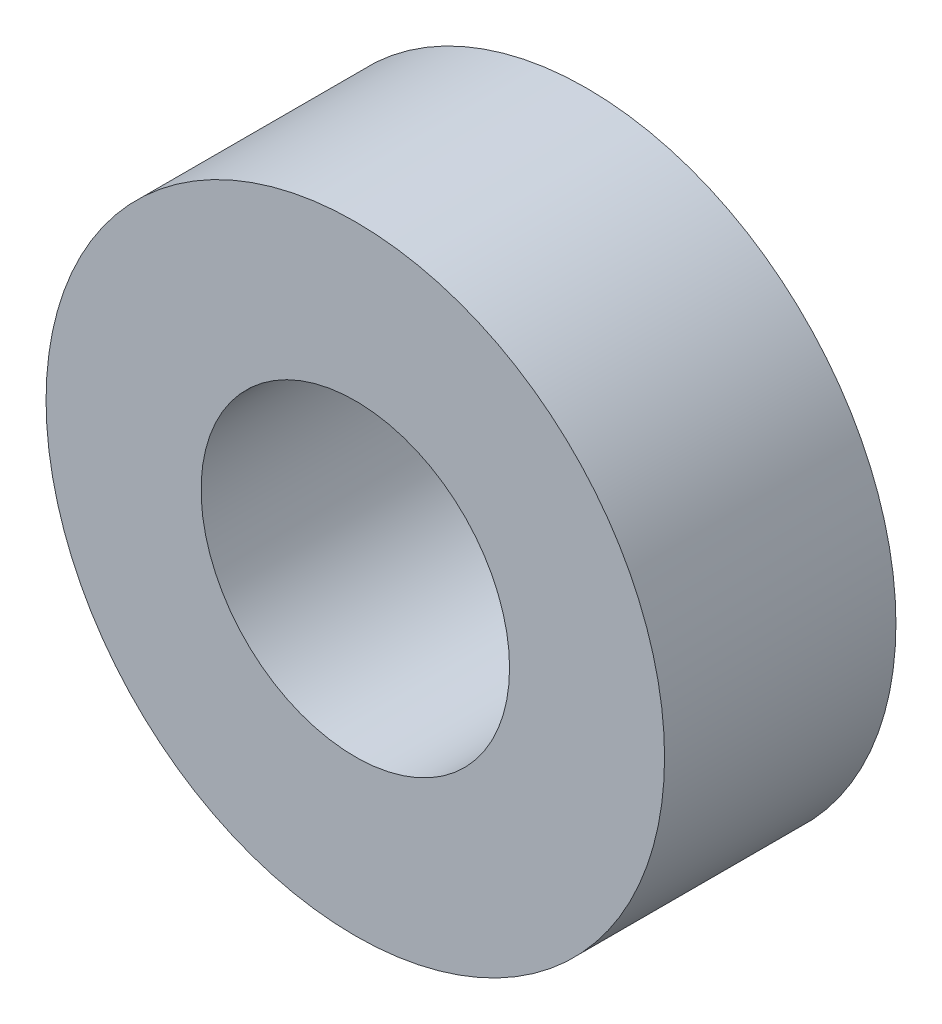
SolidWorks part; units mm, degrees
material "Tin Bearing Bronze"
ref_plane "Front Plane" through (0, 0, 0) normal (0, 0, 1) x (1, 0, 0)
ref_plane "Top Plane" through (0, 0, 0) normal (0, 1, 0) x (1, 0, 0)
ref_plane "Right Plane" through (0, 0, 0) normal (1, 0, 0) x (0, 0, -1)
sketch "Sketch1" plane through (0, 0, 0) normal (0, 0, 1) x (1, 0, 0)
  circle A0 centre (0, 0) radius 4.01
  circle A1 centre (0, 0) radius 2
  dimension "D1" = 8.02
  dimension "ID" = 4
extrude "Extrude1" add sketch "Sketch1" along normal mid plane 3
sketch "Sketch2" plane through (0, 0, 0) normal (1, 0, 0) x (0, 0, -1)
  line L0 (-1.5, -2) -> (1.5, -2) construction
  line L3 (1.5, 2) -> (-1.5, 2) construction
  line L5 (-1.5, -2) -> (1.5, -2)
  line L6 (1.5, 2) -> (-1.5, 2)
sketch "Sketch4" plane through (0, 0, 1.5) normal (0, 0, 1) x (1, 0, 0)
  line L0 (0, 0) -> (-1.4142, 1.4142)
  line L1 (0, -55) -> (0, 55) construction
  circle A0 centre (0, 0) radius 2 construction
  dimension "D1" = 45
ref_axis "Center Axis 1" through (0, 0, -22) along (0, 0, 1)
ref_plane "Contaxt Plane 1" through (0, 0, 1.5) normal (0, 0, 1) x (1, 0, 0)
ref_plane "Contact Plane 2" through (0, 0, -1.5) normal (0, 0, -1) x (-1, 0, 0)
